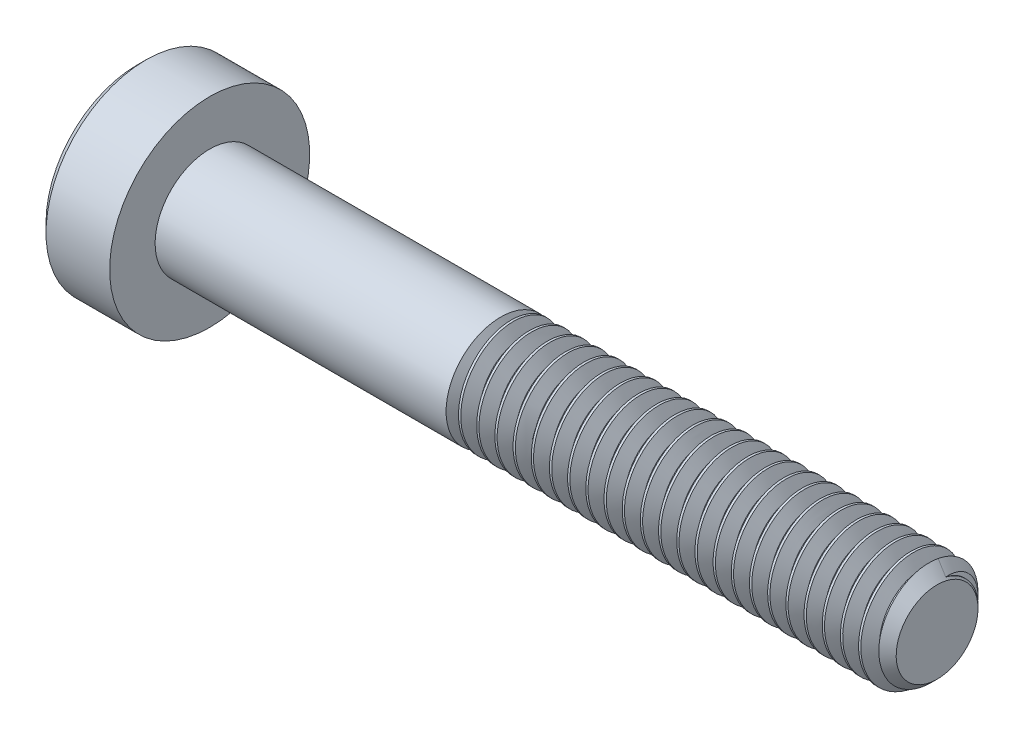
SolidWorks part; units mm, degrees
ref_plane "Front Plane" through (0, 0, 0) normal (0, 0, 1) x (1, 0, 0)
ref_plane "Top Plane" through (0, 0, 0) normal (0, 1, 0) x (1, 0, 0)
ref_plane "Right Plane" through (0, 0, 0) normal (1, 0, 0) x (0, 0, -1)
sketch "Sketch1" plane through (0, 0, 0) normal (0, 0, 1) x (1, 0, 0)
  line L0 (10, 0) -> (-10, 0) construction
  line L1 (10, 1.5) -> (10, -1.5) construction
  line L2 (-10, 2.75) -> (-10, -2.75) construction
  line L3 (-10, 2.75) -> (-11.75, 2.75) construction
  line L4 (-11.75, 2.75) -> (-12, 2.5) construction
  line L5 (-12, 2.5) -> (-12, -2.5) construction
  line L6 (-12, -2.5) -> (-11.75, -2.75) construction
  line L7 (-11.75, -2.75) -> (-10, -2.75) construction
  line L8 (-2, 1.5) -> (-2, -1.5) construction
  point P7 (-10.38, 0)
  point P12 (8, -1.5)
  dimension "D1" = 45
  dimension "Dec." = 3
  dimension "Length" = 20
  dimension "Head Dia" = 5.5
  dimension "Head Height" = 2
  dimension "Hex Depth" = 1.62
  dimension "Chamfer" = 0.25
  dimension "D2" = 2
  dimension "Thread Length" = 12
ref_plane "Plane1" through (10, 0, 0) normal (1, 0, 0) x (0, 0, -1)
ref_plane "Plane2" through (-12, 0, 0) normal (1, 0, 0) x (0, 0, -1)
sketch "Sketch2" plane through (10, 0, 0) normal (1, 0, 0) x (0, 0, -1)
  circle A0 centre (0, 0) radius 1.5
extrude "Boss-Extrude1" add sketch "Sketch2" against normal up to vertex (12 mm away) up to point (-2, 1.5, 0)
sketch "Sketch3" plane through (10, 0, 0) normal (1, 0, 0) x (0, 0, -1)
  circle A0 centre (0, 0) radius 1.5 construction
  circle A1 centre (0, 0) radius 1.5
curve "Helix/Spiral1" pitch 0.5 height 12.5 radius 1.5 centre (10, 0, 0) axis (-1, 0, 0) start towards (0, 1, 0) parameters "Pitch"=0.5
chamfer "Chamfer1" distance 0.375 angle 45 1 edges at (10, 0, -1.5)
sketch "Sketch5" plane through (0, 0, 0) normal (0, 0, 1) x (1, 0, 0)
  line L0 (9.7812, 1.5) -> (10.2188, 1.5)
  line L1 (10.2188, 1.5) -> (10.0313, 1.1752)
  line L2 (10.0313, 1.1752) -> (9.9688, 1.1752)
  line L3 (9.9688, 1.1752) -> (9.7812, 1.5)
  line L4 (10, 1.1752) -> (10, 1.5) construction
  line L5 (9.875, 1.3376) -> (10.125, 1.3376) construction
  dimension "D1" = 60
  dimension "D2" = 0.25
  dimension "D3" = 0.0625
sweep "Cut-Sweep1" cut profiles "Sketch5" path "Helix/Spiral1" align with end faces yes
sketch "Sketch4" plane through (-12, 0, 0) normal (1, 0, 0) x (0, 0, -1)
  line L0 (-2.75, 0.7937) -> (2.75, 0.7937) construction
  line L1 (0, 1.1547) -> (-1, 0.5774)
  line L2 (-1, 0.5774) -> (-1, -0.5774)
  line L3 (-1, -0.5774) -> (0, -1.1547)
  line L4 (0, -1.1547) -> (1, -0.5774)
  line L5 (1, -0.5774) -> (1, 0.5774)
  line L6 (1, 0.5774) -> (0, 1.1547)
  line L7 (0, 0) -> (0, 0.7937) construction
  circle A0 centre (0, 0) radius 1 construction
  dimension "Hex Size" = 2
  dimension "D1" = 5.5
  dimension "D2" = 0.7937
sketch "Sketch10" plane through (0, 0, 0) normal (0, 0, 1) x (1, 0, 0)
  line L0 (-10, 0) -> (-1.134, 0) construction
  line L1 (-1.134, 0) -> (-2, 1.5)
  line L2 (-2, 1.5) -> (-10, 1.5)
  line L3 (-10, 1.5) -> (-10, 0)
  line L4 (-10, 2.75) -> (-10, -2.75) construction
  line L5 (-10, 0) -> (-1.134, 0)
  dimension "D1" = 60
revolve "Revolve2" add sketch "Sketch10" angle 360 about L0
sketch "Sketch6" plane through (0, 0, 0) normal (0, 0, 1) x (1, 0, 0)
  line L0 (-11.75, 2.75) -> (-12, 2.5) construction
  line L1 (-10, 2.75) -> (-11.75, 2.75) construction
  line L2 (-10, 2.75) -> (-10, -2.75) construction
  line L3 (-12, 2.5) -> (-12, -2.5) construction
  line L4 (-11.75, 2.75) -> (-12, 2.5)
  line L5 (-10, 2.75) -> (-11.75, 2.75)
  line L6 (-10, 2.75) -> (-10, 0)
  line L7 (-12, 2.5) -> (-12, 0)
  line L8 (-10, 0) -> (-12, 0) construction
  line L9 (-10, 0) -> (-12, 0)
revolve "Revolve1" add sketch "Sketch6" angle 360 about L8
extrude "Cut-Extrude1" cut sketch "Sketch4" along normal up to vertex (1.62 mm away) up to point (-10.38, 0, 0)
sketch "Sketch8" plane through (-12, 0, 0) normal (-1, 0, 0) x (0, 0, 1)
  circle A1 centre (0, 0) radius 1.1547
extrude "Cut-Extrude2" cut sketch "Sketch8" against normal through all draft 45
equation "\"D3@Helix/Spiral1\" = \"Thread Length@Sketch1\"+\"Pitch@Helix/Spiral1\""
equation "\"D3@Sketch5\" = \"Pitch@Helix/Spiral1\"*.125"
equation "\"D2@Sketch5\" = \"Pitch@Helix/Spiral1\"*.50"
equation "\"D1@Chamfer1\" = \"Pitch@Helix/Spiral1\"*.75"
equation "\"D2@Sketch1\" = \"Pitch@Helix/Spiral1\"*4"
equation "\"D1@Sketch4\" = \"Head Dia@Sketch1\""
equation "\"Chamfer@Sketch1\" = \"Head Height@Sketch1\"/8"
